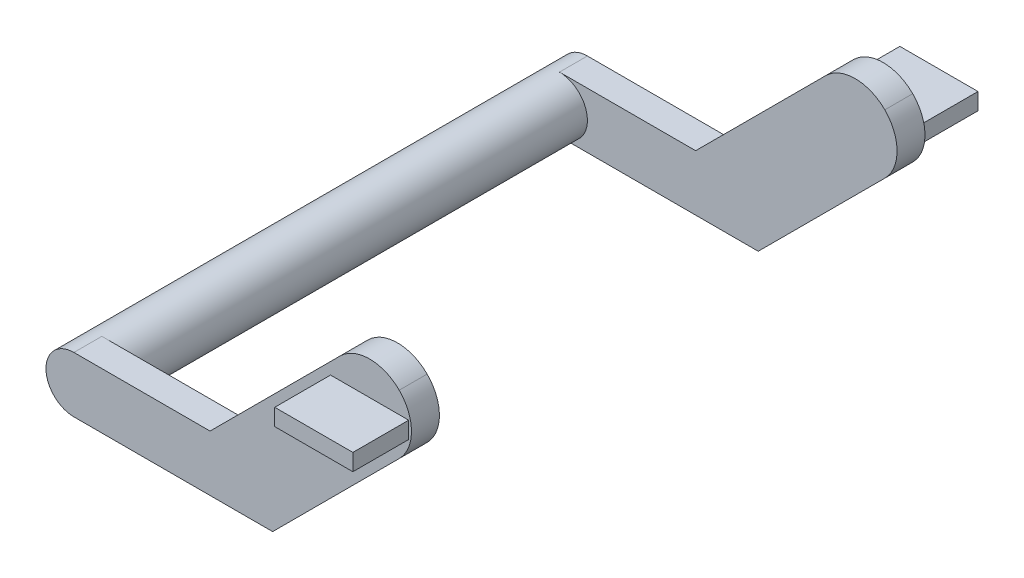
SolidWorks part; units mm, degrees
ref_plane "前视基准面" through (0, 0, 0) normal (0, 0, 1) x (1, 0, 0)
ref_plane "上视基准面" through (0, 0, 0) normal (0, 1, 0) x (1, 0, 0)
ref_plane "右视基准面" through (0, 0, 0) normal (1, 0, 0) x (0, 0, -1)
other "Configuration Table"
sketch "草图1" plane through (0, 0, 0) normal (0, 0, 1) x (1, 0, 0)
  circle A0 centre (0, 0) radius 5
  dimension "D1" = 10
extrude "凸台-拉伸1" add sketch "草图1" along normal blind 41 and the other way blind 41
sketch "草图2" plane through (0, 0, 41) normal (0, 0, 1) x (1, 0, 0)
  line L2 (-5, 0) -> (5, 0) construction
  line L7 (0, 5) -> (24.3934, 5)
  line L8 (24.3934, 5) -> (52.981, 33.5876)
  line L9 (52.981, 33.5876) -> (63.5876, 22.981)
  line L10 (63.5876, 22.981) -> (35.6066, -5)
  line L11 (35.6066, -5) -> (0, -5)
  line L12 (24.3934, 5) -> (35.6066, -5) construction
  line L13 (30, 0) -> (58.2843, 28.2843) construction
  line L14 (0, 0) -> (30, 0) construction
  arc A0 (0, 5) -> (0, -5) centre (0, 0) ccw
  circle A1 centre (0, 0) radius 5 construction
  dimension "D1" = 15
  dimension "D2" = 40
  dimension "D3" = 30
  dimension "D4" = 135
extrude "凸台-拉伸2" add sketch "草图2" along normal blind 5
fillet "圆角1" radius 7.5 2 edges at (63.5876, 22.981, 43.5) (52.981, 33.5876, 43.5)
mirror "镜向1" about plane through (0, 0, 0) normal (0, 0, 1) of "凸台-拉伸2", "圆角1"
sketch "草图3" plane through (0, 0, 46) normal (0, 0, 1) x (1, 0, 0)
  line L5 (45.981, 21.481) -> (59.981, 21.481)
  line L6 (45.981, 21.481) -> (45.981, 24.481)
  line L7 (45.981, 24.481) -> (59.981, 24.481)
  line L8 (59.981, 21.481) -> (59.981, 24.481)
  line L9 (45.981, 21.481) -> (59.981, 24.481) construction
  line L10 (45.981, 24.481) -> (59.981, 21.481) construction
  point P0 (52.981, 22.981)
  dimension "D1" = 14
  dimension "D2" = 3
extrude "凸台-拉伸3" add sketch "草图3" along normal blind 10
mirror "镜向2" about plane through (0, 0, 0) normal (0, 0, 1) of "凸台-拉伸3"
